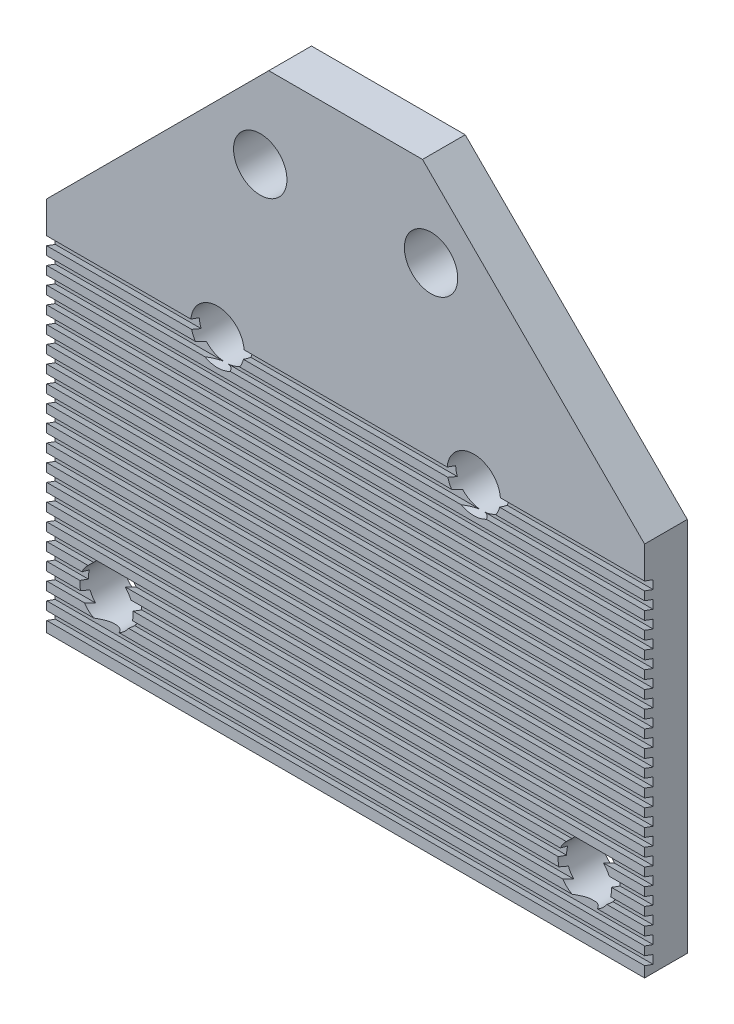
SolidWorks part; units mm, degrees
material "6061-T6 (SS)"
ref_plane "Front Plane" through (0, 0, 0) normal (0, 0, 1) x (1, 0, 0)
ref_plane "Top Plane" through (0, 0, 0) normal (0, 1, 0) x (1, 0, 0)
ref_plane "Right Plane" through (0, 0, 0) normal (1, 0, 0) x (0, 0, -1)
sketch "Sketch1" plane through (0, 0, 0) normal (0, 0, 1) x (1, 0, 0)
  line L1 (-44.45, -44.45) -> (44.45, -44.45)
  line L2 (-44.45, -44.45) -> (-44.45, 44.45)
  line L3 (-44.45, 44.45) -> (44.45, 44.45)
  line L4 (44.45, -44.45) -> (44.45, 44.45)
  line L5 (-44.45, -44.45) -> (44.45, 44.45) construction
  line L6 (-44.45, 44.45) -> (44.45, -44.45) construction
  point P0 (0, 0)
  dimension "D1" = 88.9
  dimension "D2" = 88.9
extrude "Boss-Extrude1" add sketch "Sketch1" along normal mid plane 6.35
hole_wizard "Tap Drill for 3/8-16 Tap2" positions "Sketch6" profile "Sketch7" hole size "3/8-16" standard "ANSI Inch" end condition through all
sketch "Sketch6" plane through (0, 0, 3.175) normal (0, 0, 1) x (1, 0, 0)
  line L0 (-12.7, 31.75) -> (12.7, 31.75) construction
  line L2 (-19.05, 6.35) -> (19.05, 6.35) construction
  line L4 (44.45, 44.45) -> (-44.45, 44.45) construction
  line L5 (-44.45, 44.45) -> (-44.45, -44.45) construction
  line L6 (-44.45, -44.45) -> (44.45, -44.45) construction
  line L7 (44.45, -44.45) -> (44.45, 44.45) construction
  point P9 (0, 6.35)
  point P10 (0, 31.75)
  point P15 (-12.7, 31.75)
  point P18 (12.7, 31.75)
  point P21 (19.05, 6.35)
  point P24 (-19.05, 6.35)
  point P28 (-35.56, -35.56)
  point P30 (35.56, -35.56)
  dimension "D1" = 25.4
  dimension "D2" = 38.1
  dimension "D3" = 25.4
  dimension "D4" = 12.7
  dimension "D5" = 8.89
  dimension "D6" = 8.89
  dimension "D7" = 8.89
sketch "Sketch7" plane through (-12.7, 31.75, 3.175) normal (1, 0, 0) x (0, -1, 0)
  line L0 (0, 0) -> (0, 6.35)
  line L1 (0, 6.35) -> (3.9687, 6.35)
  line L2 (3.9687, 6.35) -> (3.9687, 0)
  line L5 (3.9687, 0) -> (0, 0)
  line L11 (0, -6.35) -> (0, 107.95) construction
  dimension "Thru Hole Dia." = 7.9375
  dimension "Thru Hole Depth" = 6.35
chamfer "Chamfer1" distance 33.02 angle 45 2 edges at (44.45, 44.45, 0) (-44.45, 44.45, 0)
sketch "Sketch9" plane through (0, 0, 0) normal (-1, 0, 0) x (0, 0, 1)
  line L0 (3.175, -42.8625) -> (1.905, -43.3247)
  line L1 (3.175, 11.43) -> (3.175, -44.45) construction
  line L2 (1.905, -43.3247) -> (1.905, -42.0547)
  line L3 (3.175, -44.45) -> (-3.175, -44.45) construction
  line L5 (1.905, -42.0547) -> (3.175, -41.5925)
  line L6 (3.175, -41.5925) -> (3.175, -42.8625)
  dimension "D1" = 70
  dimension "D2" = 70
  dimension "D3" = 1.5875
  dimension "D4" = 1.27
  dimension "D5" = 1.27
extrude "Cut-Extrude6" cut sketch "Sketch9" against normal through all both and the other way through all
pattern_linear "LPattern2" count 20 spacing 2.54 along (0, 1, 0) of "Cut-Extrude6"
equation "\"D7@Sketch6\"=\"D5@Sketch6\""
